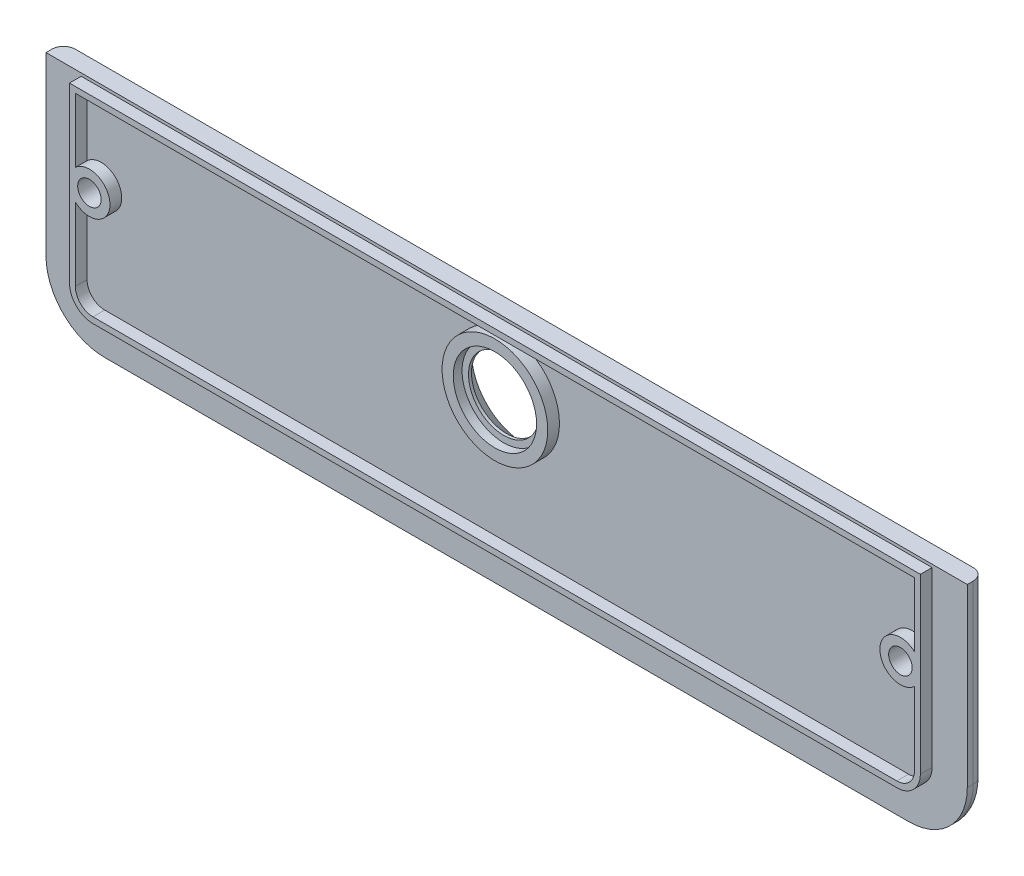
SolidWorks part; units mm, degrees
ref_plane "Front Plane" through (0, 0, 0) normal (0, 0, 1) x (1, 0, 0)
ref_plane "Top Plane" through (0, 0, 0) normal (0, 1, 0) x (1, 0, 0)
ref_plane "Right Plane" through (0, 0, 0) normal (1, 0, 0) x (0, 0, -1)
sketch "Sketch1" plane through (0, 0, 0) normal (0, 0, 1) x (1, 0, 0)
  line L0 (0, 35.5) -> (147, 35.5)
  line L1 (5, 0) -> (142, 0)
  line L2 (0, 5) -> (0, 55.5)
  line L3 (0, 55.5) -> (147, 55.5)
  line L4 (147, 5) -> (147, 55.5)
  line L5 (0, 42.5) -> (147, 42.5)
  line L6 (73.5, 0) -> (73.5, 55.5) construction
  line L7 (63.5, 0) -> (63.5, 35.5) construction
  arc A0 (142, 0) -> (147, 5) centre (142, 5) ccw
  arc A1 (5, 0) -> (0, 5) centre (5, 5) cw
  circle A2 centre (4.4, 17.75) radius 1.75
  circle A3 centre (142.6, 17.75) radius 1.75
  point P11 (147, 0)
  point P14 (0, 0)
  point P24 (63.5, 17.75)
  dimension "D5" = 5
  dimension "D6" = 3.5
  dimension "D1" = 147
  dimension "D2" = 55.5
  dimension "D3" = 35.5
  dimension "D4" = 42.5
  dimension "D7" = 138.2
  dimension "D8" = 10
sketch "Sketch2" plane through (0, 0, 0) normal (0, 0, 1) x (1, 0, 0)
  line L17 (-5, 35) -> (152, 35)
  line L18 (0, 35.5) -> (147, 35.5) construction
  line L21 (152, 60.5) -> (-5, 60.5)
  line L22 (152, 5) -> (152, 60.5)
  line L23 (-5, 60.5) -> (-5, 5)
  line L24 (5, -5) -> (142, -5)
  line L26 (152, 5) -> (152, 35)
  line L27 (-5, 35) -> (-5, 5)
  line L28 (5, -5) -> (142, -5)
  arc A10 (-5, 5) -> (5, -5) centre (5, 5) ccw
  arc A11 (142, -5) -> (152, 5) centre (142, 5) ccw
  arc A12 (-5, 5) -> (5, -5) centre (5, 5) ccw
  arc A13 (142, -5) -> (152, 5) centre (142, 5) ccw
  dimension "D2" = 0.5
  dimension "D1" = 5
extrude "Boss-Base" add sketch "Sketch2" along normal blind 3
sketch "Sketch3" plane through (0, 0, 3) normal (0, 0, 1) x (1, 0, 0)
  line L0 (152, 35) -> (-5, 35) construction
  line L5 (1, 5) -> (1, 34.5)
  line L6 (1, 34.5) -> (146, 34.5)
  line L7 (2, 33.5) -> (145, 33.5)
  line L8 (146, 34.5) -> (146, 5)
  line L9 (142, 1) -> (5, 1)
  line L10 (145, 55.5) -> (145, 5)
  line L11 (2, 5) -> (2, 55.5)
  line L12 (142, 2) -> (5, 2)
  line L14 (2, 5) -> (2, 17.4525)
  line L15 (142, 2) -> (5, 2)
  line L16 (2, 22.5475) -> (2, 33.5)
  line L17 (2, 5) -> (2, 33.5) construction
  line L18 (73.5, 0) -> (73.5, 55.5) construction
  line L19 (145, 33.5) -> (145, 5) construction
  line L20 (73.5, 0) -> (73.5, 55.5) construction
  line L21 (145, 22.5475) -> (145, 33.5)
  line L22 (145, 5) -> (145, 17.4525)
  arc A0 (142, 1) -> (146, 5) centre (142, 5) ccw
  arc A1 (1, 5) -> (5, 1) centre (5, 5) ccw
  arc A4 (142, 2) -> (145, 5) centre (142, 5) ccw
  arc A5 (2, 5) -> (5, 2) centre (5, 5) ccw
  arc A6 (142, 2) -> (145, 5) centre (142, 5) ccw
  arc A7 (2, 5) -> (5, 2) centre (5, 5) ccw
  circle A8 centre (4.4, 20) radius 2
  arc A10 (2, 17.4525) -> (2, 22.5475) centre (4.4, 20) ccw
  arc A11 (145, 17.4525) -> (145, 22.5475) centre (142.6, 20) cw
  circle A12 centre (142.6, 20) radius 2
  dimension "D4" = 4
  dimension "D5" = 7
  dimension "D2" = 1.5
  dimension "D6" = 20
  dimension "D1" = 2
  dimension "D3" = 1
extrude "Boss-Fit" add sketch "Sketch3" along normal blind 2
sketch "Sketch4" plane through (0, 0, 3) normal (0, 0, 1) x (1, 0, 0)
  circle A0 centre (4.4, 20) radius 2 construction
  circle A1 centre (4.4, 20) radius 2
  circle A2 centre (142.6, 20) radius 2 construction
  circle A3 centre (142.6, 20) radius 2
extrude "Cut-Screws" cut sketch "Sketch4" against normal offset from surface (2 mm away) 1 up to face at (73.5, 10.9763, 0)
fillet "Fillet1" radius 2 5 edges at (-5, 20, 0) (-2.0711, -2.0711, 0) (152, 20, 0) (149.0711, -2.0711, 0) (73.5, -5, 0)
sketch "Sketch10" plane through (0, 0, 0) normal (0, 0, -1) x (-1, 0, 0)
  line L0 (-140.7988, 14) -> (-145, 8)
  line L7 (-145, 8) -> (-142.25, 8)
  line L8 (-142.25, 8) -> (-138.0488, 14)
  line L9 (-138.0488, 14) -> (-140.7988, 14)
  line L10 (-136.0488, 14) -> (-144.4512, 2)
  line L11 (-144.4512, 2) -> (-141.7012, 2)
  line L12 (-141.7012, 2) -> (-133.2988, 14)
  line L13 (-133.2988, 14) -> (-136.0488, 14)
  line L14 (-135.5, 8) -> (-139.7012, 2)
  line L15 (-139.7012, 2) -> (-136.9512, 2)
  line L16 (-136.9512, 2) -> (-132.75, 8)
  line L17 (-132.75, 8) -> (-135.5, 8)
  line L18 (-142, -3) -> (-5, -3) construction
  line L19 (-150, 35) -> (-150, 5) construction
  dimension "D1" = 12
  dimension "D2" = 6
  dimension "D3" = 2.75
  dimension "D4" = 2
  dimension "D5" = 2
  dimension "D6" = 55
  dimension "D7" = 5
  dimension "D8" = 5
extrude "Cut-Voron" cut sketch "Sketch10" against normal blind 0.6
sketch "Sketch8" plane through (0, 0, 3) normal (0, 0, 1) x (1, 0, 0)
  line L0 (73.5, 2) -> (73.5, 54.9904) construction
  line L1 (5, 2) -> (142, 2) construction
  circle A0 centre (73.5, 24) radius 9
  dimension "D2" = 18
  dimension "D1" = 24
extrude "Boss-Bearing" add sketch "Sketch8" along normal blind 2 contours A0
sketch "Sketch12" plane through (0, 0, 5) normal (0, 0, 1) x (1, 0, 0)
  circle A0 centre (73.5, 24) radius 7.1
  dimension "D1" = 14.2
extrude "Cut-Bearing1" cut sketch "Sketch12" against normal blind 1.5
sketch "Sketch11" plane through (0, 0, 5) normal (0, 0, 1) x (1, 0, 0)
  circle A0 centre (73.5, 24) radius 6
  circle A1 centre (73.5, 24) radius 9 construction
  dimension "D1" = 12
extrude "Cut-Bearing2" cut sketch "Sketch11" against normal through all
chamfer "Chamfer2" distance 3 angle 45 1 edges at (79.5, 24, 0)
equation "\"width\"=147"
equation "\"D1@Sketch1\"=\"width\""
equation "\"height\"=42.5"
equation "\"height_outside\"=55.5"
equation "\"D2@Sketch1\"=\"height_outside\""
equation "\"height_inside\"=35.5"
equation "\"D3@Sketch1\"=\"height_inside\""
equation "\"D4@Sketch1\"=\"height\""
